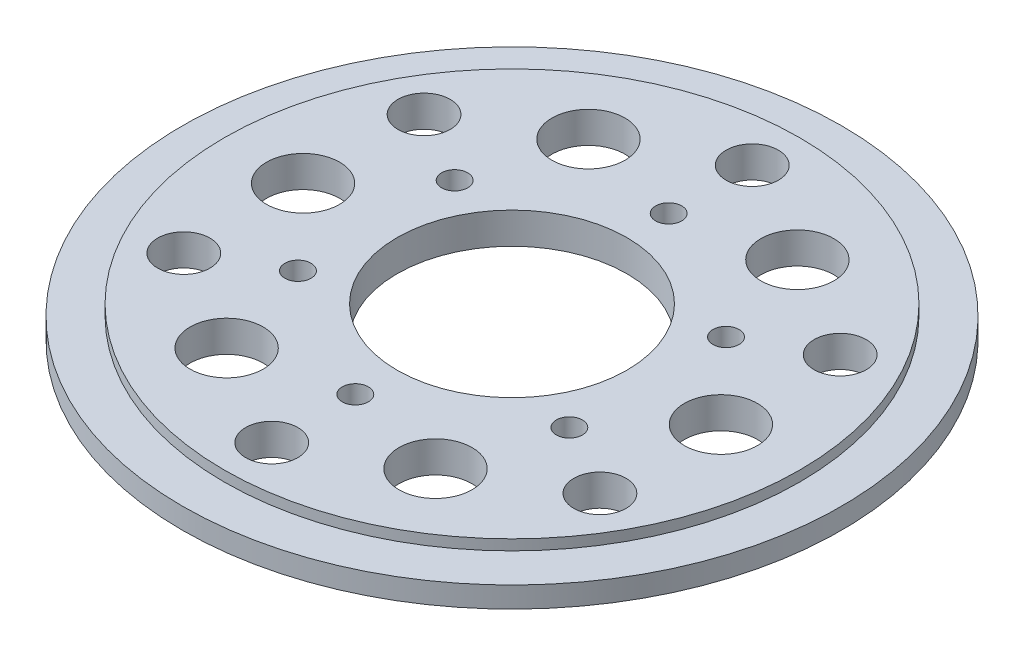
SolidWorks part; units mm, degrees
ref_plane "Front Plane" through (0, 0, 0) normal (0, 0, 1) x (1, 0, 0)
ref_plane "Top Plane" through (0, 0, 0) normal (0, 1, 0) x (1, 0, 0)
ref_plane "Right Plane" through (0, 0, 0) normal (1, 0, 0) x (0, 0, -1)
sketch "Sketch1" plane through (0, 0, 0) normal (0, 1, 0) x (1, 0, 0)
  circle A0 centre (0, 0) radius 27.55
  circle A1 centre (0, 0) radius 11
  circle A2 centre (0, 0) radius 31.55
  dimension "D1" = 55.1
  dimension "D3" = 22
  dimension "D2" = 4
extrude "Boss-Extrude1" add sketch "Sketch1" along normal blind 3 contours A0 A1 region at (-26.7708, 0, 0)
extrude "Boss-Extrude2" add sketch "Sketch1<3>" along normal blind 2 contours A2 A0 region at (-30.6576, 0, 0)
sketch "Sketch1<3>" plane through (0, 0, 0) normal (0, 1, 0) x (1, 0, 0) same geometry as "Sketch1"
hole_wizard "M3x0.5 Tapped Hole1" positions "Sketch2" profile "Sketch4" tap size "M3x0.5" standard "ANSI Metric" end condition through all
sketch "Sketch2" plane through (0, 3, 0) normal (0, 1, 0) x (1, 0, 0)
  line L0 (0, 0) -> (0, 15) construction
  point P0 (0, 15)
  dimension "D1" = 15
sketch "Sketch4" plane through (0, 3, -15) normal (1, 0, 0) x (0, 0, 1)
  line L0 (0, 0) -> (0, 3)
  line L1 (0, 3) -> (1.25, 3)
  line L2 (1.25, 3) -> (1.25, 0)
  line L5 (1.25, 0) -> (0, 0)
  line L11 (0, -6.35) -> (0, 107.95) construction
  dimension "Thru Tap Drill Dia." = 2.5
  dimension "Thru Tap Drill Depth" = 3
sketch "Sketch6" plane through (0, 3, 0) normal (0, 1, 0) x (1, 0, 0)
  line L0 (0, 0) -> (20, 0) construction
  line L1 (0, 0) -> (0, 23) construction
  circle A0 centre (20, 0) radius 3.5
  circle A1 centre (0, 23) radius 2.5
  dimension "D2" = 7
  dimension "D4" = 5
  dimension "D1" = 20
  dimension "D3" = 23
extrude "Cut-Extrude1" cut sketch "Sketch6" against normal through all
pattern_circular "CirPattern1" count 6 over 360 about axis through (0, 3, 0) along (0, -1, 0) of "M3x0.5 Tapped Hole1", "Cut-Extrude1" reverse direction yes
equation "\"Ratio\"= 15"
equation "\"Hull Diameter\"= 3.5in"
equation "\"Fixed Ring Diameter\"= 76"
equation "\"Fixed Pin Diameter\"= 6"
equation "\"Output Ring Diameter\"= 40"
equation "\"Output Pin Diameter\"= 6"
equation "\"Disk Bearing Inner Diameter\"= 9"
equation "\"Disk Bearing Outer Diameter\"= 17"
equation "\"Disk Bearing Height\"= 5"
equation "\"Shaft Bearing Inner Diameter\"= 15"
equation "\"Shaft Bearing Outer Diameter\"= 21"
equation "\"Shaft Bearing Height\"= 4"
equation "\"Eccentricity\"= 1.5"
equation "\"Disk Height\"= 8"
equation "\"Disk Spacing\"= 5"
equation "\"Hull Height\"= 40"
equation "\"Shaft End Bearing Inner Diameter\"= 12"
equation "\"Shaft End Bearing Outer Diameter\"= 18"
equation "\"Shaft End Bearing Height\"= 4"
equation "\"Output Bearing Inner Diameter\"= 55"
equation "\"Output Bearing Outer Diameter\"= 72"
equation "\"Outer Bearing Height\"= 9"
equation "\"D1@Sketch1\"=\"Output Bearing Inner Diameter\"+0.1"
